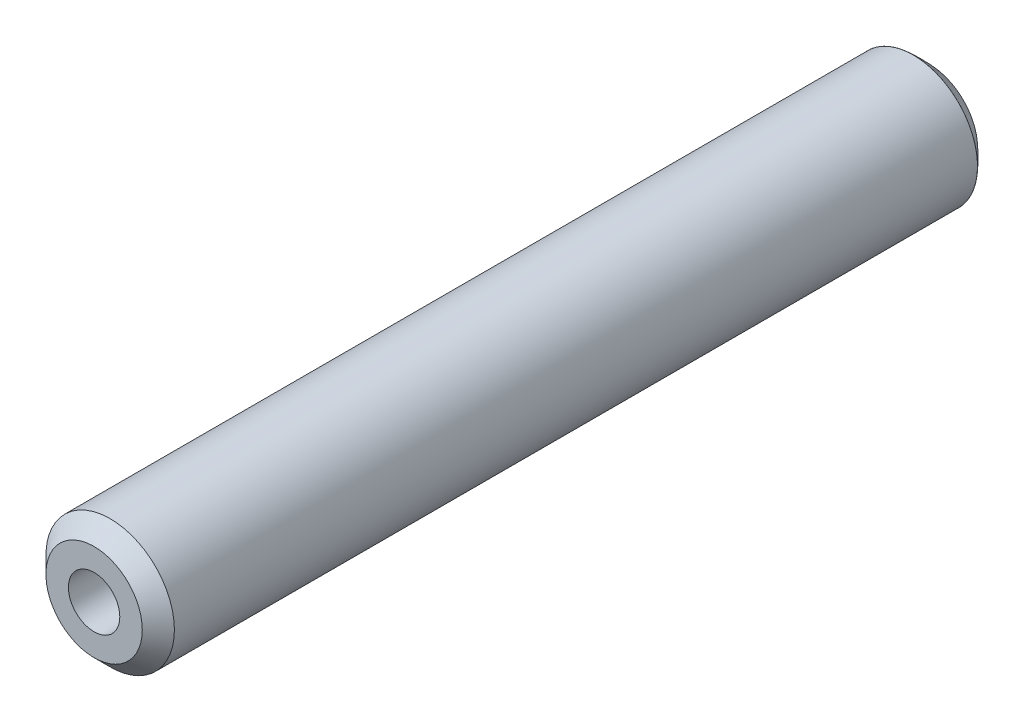
SolidWorks part; units mm, degrees
material "2A12"
ref_plane "前视基准面" through (0, 0, 0) normal (0, 0, 1) x (1, 0, 0)
ref_plane "上视基准面" through (0, 0, 0) normal (0, 1, 0) x (1, 0, 0)
ref_plane "右视基准面" through (0, 0, 0) normal (1, 0, 0) x (0, 0, -1)
sketch "草图2" plane through (0, 0, 0) normal (0, 0, 1) x (1, 0, 0)
  line L0 (0, 19.5) -> (0, -19.5) construction
  line L1 (-19, 19.5) -> (19, 19.5)
  line L2 (-19, 19.5) -> (-19, -19.5)
  line L3 (-19, -19.5) -> (19, -19.5)
  line L4 (19, 19.5) -> (19, -19.5)
  dimension "D1" = 38
  dimension "D2" = 39
extrude "拉伸1" add sketch "草图2" along normal blind 2
sketch "草图3" plane through (0, 0, 2) normal (0, 0, 1) x (1, 0, 0)
  line L0 (-14, 16.5) -> (-14, -16.5) construction
  line L1 (0, 0) -> (-14, 0) construction
  line L2 (-19, 19.5) -> (-19, -19.5) construction
  circle A0 centre (-14, 16.5) radius 1.75
  circle A1 centre (-14, -16.5) radius 1.75
  dimension "D2" = 3.5
  dimension "D1" = 33
  dimension "D3" = 5
chamfer "倒角2" [suppressed] distance 22 angle 30
chamfer "倒角3" distance 1 angle 45 2 edges at (-19, -19.5, 1) (-19, 19.5, 1)
sketch "草图4" plane through (0, 0, 2) normal (0, 0, 1) x (1, 0, 0)
  line L0 (8.205, 5.2066) -> (-4.205, -5.2066) construction
  line L1 (2, 0) -> (2, 7.25) construction
  line L2 (-3.5538, 4.6602) -> (7.5538, -4.6602) construction
  line L3 (2, 0) -> (19, 0) construction
  line L4 (-19, 18.5) -> (-19, -18.5) construction
  line L5 (19, -19.5) -> (19, 19.5) construction
  circle A0 centre (2, 0) radius 8.1 construction
  circle A1 centre (2, 0) radius 7.25 construction
  dimension "D1" = 16.2
  dimension "D2" = 14.5
  dimension "D3" = 50
  dimension "D4" = 50
  dimension "D5" = 21
hole_wizard "M1.6 螺纹孔1" [suppressed] positions "3D草图2" profile "草图6" tap size "M1.6" standard "GB"
sketch3d "3D草图2"
  point P3 (13.145, 5.2066, 2)
  point P6 (12.4938, -4.6602, 2)
  point P9 (0.735, -5.2066, 2)
  point P12 (1.3862, 4.6602, 2)
sketch "草图6" plane through (13.145, 5.2066, 2) normal (1, 0, 0) x (0, -1, 0)
  line L0 (0, 0) -> (0, 4.6255)
  line L1 (0, 4.6255) -> (0.625, 4.25)
  line L2 (0.625, 4.25) -> (0.625, 0)
  line L5 (0.625, 0) -> (0, 0)
  line L10 (0, 4.6255) -> (-0.625, 4.25) construction
  line L11 (0, -6.35) -> (0, 107.95) construction
  dimension "螺纹孔钻头直径" = 1.25
  dimension "螺纹孔钻头深度" = 4.25
  dimension "导头角度" = 118
cosmetic thread "Hole Thread1" [suppressed] parameters "D1"=2, "D2"=1.6
cosmetic thread "Hole Thread2" [suppressed] parameters "D1"=2, "D2"=1.6
cosmetic thread "Hole Thread3" [suppressed] parameters "D1"=2, "D2"=1.6
cosmetic thread "Hole Thread4" [suppressed] parameters "D1"=2, "D2"=1.6
sketch "草图7" plane through (0, 0, 2) normal (0, 0, 1) x (1, 0, 0)
  line L0 (-2.25, 0) -> (2, 0) construction
  circle A0 centre (2, 0) radius 4.25
  dimension "D1" = 8.5
extrude "拉伸3" cut sketch "草图7" against normal blind 10
sketch "草图8" plane through (0, 0, 2) normal (0, 0, 1) x (1, 0, 0)
  line L0 (19, 19.5) -> (-18, 19.5) construction
  line L1 (-17, 19.5) -> (-19, 19.5)
  line L2 (-17, 19.5) -> (-17, -19.5)
  line L3 (-17, -19.5) -> (-19, -19.5)
  line L4 (-19, 19.5) -> (-19, -19.5)
  line L5 (-18, -19.5) -> (19, -19.5) construction
  line L6 (-19, 18.5) -> (-19, -18.5) construction
  dimension "D1" = 2
extrude "拉伸4" cut sketch "草图8" against normal blind 10
chamfer "倒角4" [suppressed] distance 1.5 angle 45
fillet "圆角3" radius 2 2 edges at (-17, -19.5, 1) (-17, 19.5, 1)
sketch "Sketch1" plane through (0, 0, 2) normal (0, 0, 1) x (1, 0, 0)
  line L0 (2, 0) -> (19, 0)
  line L1 (19, -19.5) -> (19, 19.5) construction
  line L2 (7.7569, 7.557) -> (-3.7569, -7.557)
  line L3 (-3.7569, 7.557) -> (7.7569, -7.557)
  dimension "D1" = 52.7
  dimension "D2" = 19
  dimension "D3" = 52.7
hole_wizard "M2.5 Tapped Hole1" [suppressed] positions "3DSketch1" profile "Sketch2" tap size "M2.5" standard "GB"
sketch3d "3DSketch1"
  point P0 (-3.7569, -7.557, 2)
  point P3 (7.7569, 7.557, 2)
  point P7 (-3.7569, 7.557, 2)
  point P10 (7.7569, -7.557, 2)
sketch "Sketch2" plane through (-3.7569, -7.557, 2) normal (1, 0, 0) x (0, -1, 0)
  line L0 (0, 0) -> (0, 7.8659)
  line L1 (0, 7.8659) -> (1.025, 7.25)
  line L2 (1.025, 7.25) -> (1.025, 0)
  line L5 (1.025, 0) -> (0, 0)
  line L10 (0, 7.8659) -> (-1.025, 7.25) construction
  line L11 (0, -6.35) -> (0, 107.95) construction
  dimension "Tap Drill Dia." = 2.05
  dimension "Tap Drill Depth" = 7.25
  dimension "Drill Angle" = 118
cosmetic thread "Hole Thread5" [suppressed] parameters "D1"=2, "D2"=2.5
cosmetic thread "Hole Thread6" [suppressed] parameters "D1"=2, "D2"=2.5
cosmetic thread "Hole Thread7" [suppressed] parameters "D1"=2, "D2"=2.5
cosmetic thread "Hole Thread8" [suppressed] parameters "D1"=2, "D2"=2.5
fillet "Fillet1" [suppressed] radius 3
sketch "Sketch3" [suppressed] plane through (0, 0, 2) normal (0, 0, 1) x (1, 0, 0)
  line L1 (19, 19.5) -> (15, 19.5)
  line L2 (19, 19.5) -> (19, 9.5)
  line L3 (19, 9.5) -> (15, 9.5)
  line L4 (15, 19.5) -> (15, 9.5)
  line L5 (19, -19.5) -> (15, -19.5)
  line L6 (19, -19.5) -> (19, -9.5)
  line L7 (19, -9.5) -> (15, -9.5)
  line L8 (15, -19.5) -> (15, -9.5)
  dimension "D1" = 10
  dimension "D2" = 4
extrude "Extrude1" [suppressed] cut sketch "Sketch3" against normal blind 10
chamfer "Chamfer1" [suppressed] distance 5 angle 45
fillet "Fillet2" [suppressed] radius 2.5
fillet "Fillet3" [suppressed] radius 2.5
fillet "Fillet4" [suppressed] radius 2.5
chamfer "Chamfer2" [suppressed] distance 4 angle 45
sketch "草图9" plane through (0, 0, 2) normal (0, 0, 1) x (1, 0, 0)
  circle A0 centre (-15, 17.5) radius 2
  arc A2 (-15, 19.5) -> (-17, 17.5) centre (-15, 17.5) ccw construction
  circle A3 centre (-15, -17.5) radius 2
  arc A4 (-17, -17.5) -> (-15, -19.5) centre (-15, -17.5) ccw construction
extrude "凸台-拉伸1" add sketch "草图9" along normal blind 26
mirror "镜向1" about plane through (0, 0, 0) normal (0, 1, 0) of "凸台-拉伸1"
fillet "圆角4" [suppressed] radius 1.5
sketch "草图10" plane through (0, 0, 0) normal (0, 0, -1) x (-1, 0, 0)
  line L0 (15, -19.5) -> (-19, -19.5) construction
  line L1 (-19, 19.5) -> (-16, 19.5)
  line L2 (-19, 19.5) -> (-19, -19.5)
  line L3 (-19, -19.5) -> (-16, -19.5)
  line L4 (-16, 19.5) -> (-16, -19.5)
  dimension "D1" = 3
extrude "切除-拉伸1" cut sketch "草图10" against normal blind 10
fillet "圆角5" radius 2 2 edges at (16, -19.5, 1) (16, 19.5, 1)
chamfer "倒角5" distance 0.5 angle 45 10 edges at (-13, -17.5, 28) (-13, 17.5, 28) (15.4142, 18.9142, 0) (16, 0, 0) (-0.5, 19.5, 0) (15.4142, -18.9142, 0) (-16.4142, 18.9142, 0) (-0.5, -19.5, 0) (-17, 0, 0) (-16.4142, -18.9142, 0)
sketch "草图20" plane through (0, 0, 0) normal (0, 0, -1) x (-1, 0, 0)
  line L0 (3.7569, 7.557) -> (-7.7569, -7.557) construction
  line L1 (-9.5, -15.5) -> (5.5, -15.5)
  line L2 (-9.5, -15.5) -> (-9.5, 15.5)
  line L3 (-9.5, 15.5) -> (5.5, 15.5)
  line L4 (5.5, -15.5) -> (5.5, 15.5)
  line L5 (-9.5, -15.5) -> (5.5, 15.5) construction
  line L6 (-9.5, 15.5) -> (5.5, -15.5) construction
  line L7 (-14, 19.5) -> (15, 19.5) construction
  point P0 (-2, 0)
  dimension "D1" = 4
  dimension "D2" = 15
hole_wizard "M2.5 螺纹孔3" positions "3D草图7" profile "草图21" tap size "M2.5" standard "GB" end condition up to next
sketch3d "3D草图7"
  point P0 (9.5, 15.5, 0)
  point P3 (-5.5, 15.5, 0)
  point P6 (9.5, -15.5, 0)
  point P9 (-5.5, -15.5, 0)
sketch "草图21" plane through (9.5, 15.5, 0) normal (1, 0, 0) x (0, 1, 0)
  line L0 (0, 0) -> (0, 2)
  line L1 (0, 2) -> (1.025, 2)
  line L2 (1.025, 2) -> (1.025, 0)
  line L5 (1.025, 0) -> (0, 0)
  line L11 (0, -6.35) -> (0, 107.95) construction
  dimension "通孔螺纹孔钻头直径" = 2.05
  dimension "通孔螺纹孔钻头深度" = 2
cosmetic thread "孔螺蚊线7" parameters "D2"=2.5
cosmetic thread "孔螺蚊线8" parameters "D2"=2.5
cosmetic thread "孔螺蚊线9" parameters "D2"=2.5
cosmetic thread "孔螺蚊线10" parameters "D2"=2.5
hole_wizard "M2 螺纹孔1" positions "3D草图8" profile "草图22" tap size "M2" standard "GB"
sketch3d "3D草图8"
  line L0 (-15, 17.5, 27.5) -> (-15, 17.5, 28) construction
  line L1 (-15, -17.5, 27.5) -> (-15, -17.5, 28) construction
  point P0 (-15, 17.5, 28)
  point P4 (-15, -17.5, 28)
cosmetic thread "孔螺蚊线11" parameters "D1"=5, "D2"=2
cosmetic thread "孔螺蚊线12" parameters "D1"=5, "D2"=2
sketch "草图22" plane through (-15, 17.5, 28) normal (1, 0, 0) x (0, -1, 0)
  line L0 (0, 0) -> (0, 7.4807)
  line L1 (0, 7.4807) -> (0.8, 7)
  line L2 (0.8, 7) -> (0.8, 0)
  line L5 (0.8, 0) -> (0, 0)
  line L10 (0, 7.4807) -> (-0.8, 7) construction
  line L11 (0, -6.35) -> (0, 107.95) construction
  dimension "螺纹孔钻头直径" = 1.6
  dimension "螺纹孔钻头深度" = 7
  dimension "导头角度" = 118
sketch "草图23" plane through (0, 0, 0) normal (0, 0, -1) x (-1, 0, 0)
  line L0 (-2, 16.2) -> (-2, 9.8) construction
  line L1 (-0.95, 16.2) -> (-0.95, 9.8)
  line L2 (-3.05, 16.2) -> (-3.05, 9.8)
  line L3 (-14, 19.5) -> (15, 19.5) construction
  line L4 (-16, -17.5) -> (-16, 17.5) construction
  arc A0 (-0.95, 16.2) -> (-3.05, 16.2) centre (-2, 16.2) ccw
  arc A1 (-3.05, 9.8) -> (-0.95, 9.8) centre (-2, 9.8) ccw
  point P2 (-2, 13)
  dimension "D1" = 1.05
  dimension "D2" = 3.3
  dimension "D3" = 14
  dimension "D4" = 6.4
extrude "切除-拉伸2" cut sketch "草图23" against normal blind 10
mirror "镜向2" about plane through (0, 0, 0) normal (0, 1, 0) of "切除-拉伸2"
sketch "草图24" plane through (0, 0, 2) normal (0, 0, 1) x (1, 0, 0)
  line L1 (35.6453, -25.5723) -> (-35.6453, -25.5723)
  line L2 (35.6453, -25.5723) -> (35.6453, 25.5723)
  line L3 (35.6453, 25.5723) -> (-35.6453, 25.5723)
  line L4 (-35.6453, -25.5723) -> (-35.6453, 25.5723)
  line L5 (35.6453, -25.5723) -> (-35.6453, 25.5723) construction
  line L6 (35.6453, 25.5723) -> (-35.6453, -25.5723) construction
  point P0 (0, 0)
extrude "切除-拉伸3" cut sketch "草图24" against normal blind 10
sketch "草图25" plane through (0, 0, 2) normal (0, 0, -1) x (-1, 0, 0)
  circle A0 centre (15, 17.5) radius 6.5393
extrude "切除-拉伸4" cut sketch "草图25" against normal blind 32
hole_wizard "M2 螺纹孔2" positions "3D草图9" profile "草图26" tap size "M2" standard "GB"
sketch3d "3D草图9"
  line L0 (-15, -17.5, 2) -> (-15, -17.5, 27.5) construction
  point P0 (-15, -17.5, 2)
sketch "草图26" plane through (-15, -17.5, 2) normal (1, 0, 0) x (0, 1, 0)
  line L0 (0, 0) -> (0, 7.4807)
  line L1 (0, 7.4807) -> (0.8, 7)
  line L2 (0.8, 7) -> (0.8, 0)
  line L5 (0.8, 0) -> (0, 0)
  line L10 (0, 7.4807) -> (-0.8, 7) construction
  line L11 (0, -6.35) -> (0, 107.95) construction
  dimension "螺纹孔钻头直径" = 1.6
  dimension "螺纹孔钻头深度" = 7
  dimension "导头角度" = 118
cosmetic thread "孔螺蚊线13" parameters "D1"=5, "D2"=2
fillet "圆角6" radius 0.5 1 edges at (-13, -17.5, 2)
